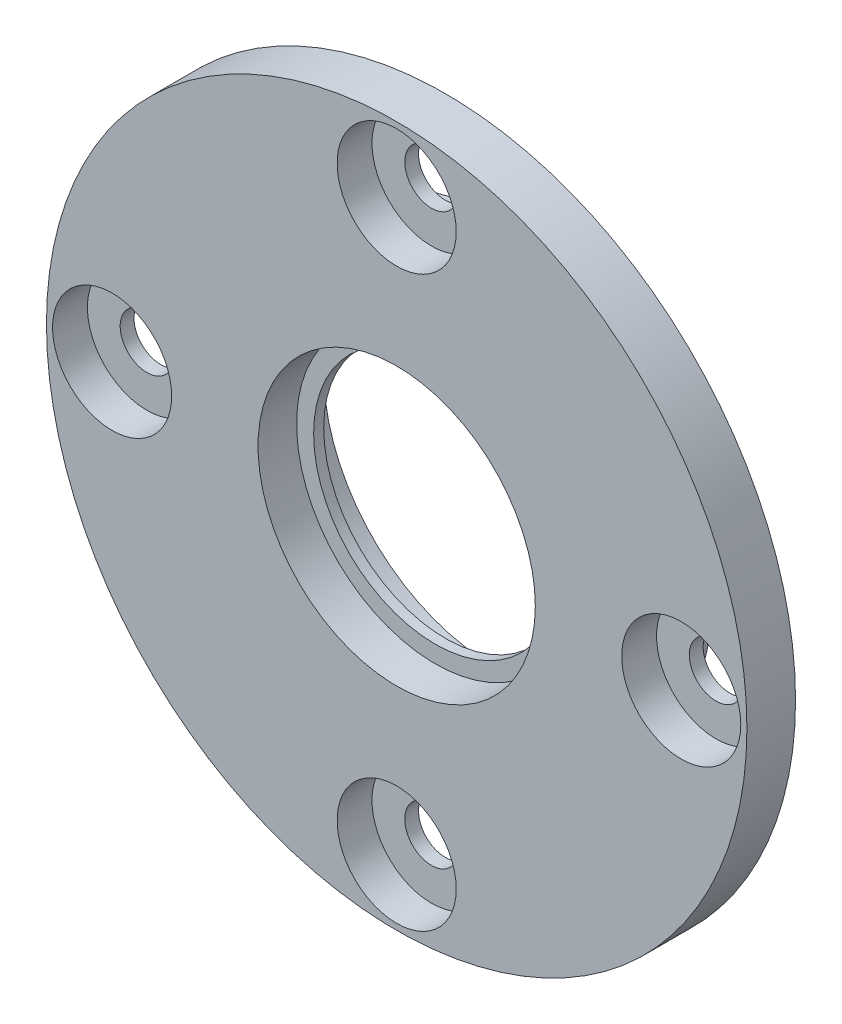
SolidWorks part; units mm, degrees
ref_plane "Front Plane" through (0, 0, 0) normal (0, 0, 1) x (1, 0, 0)
ref_plane "Top Plane" through (0, 0, 0) normal (0, 1, 0) x (1, 0, 0)
ref_plane "Right Plane" through (0, 0, 0) normal (1, 0, 0) x (0, 0, -1)
sketch "Sketch1" plane through (0, 0, 0) normal (1, 0, 0) x (0, 0, -1)
  line L0 (-109.9, -9.5) -> (-139, -9.5)
  line L5 (-1000, 0) -> (49000, 0)
  line L6 (0, -9.5) -> (0, 9.5)
  line L13 (0, 9.5) -> (-48.3, 9.5)
  line L26 (-48.3, 9.5) -> (-48.3, 14)
  line L27 (-48.3, 14) -> (-109.9, 14)
  line L32 (-109.9, 14) -> (-109.9, 9.5)
  line L34 (-155, 7) -> (-155, -7)
  line L36 (-109.9, -9.5) -> (-109.9, -14)
  line L37 (-109.9, -14) -> (-48.3, -14)
  line L38 (-48.3, -14) -> (-48.3, -9.5)
  line L39 (0, -9.5) -> (-48.3, -9.5)
  line L40 (-20.2, 36) -> (-15.2, 36)
  line L41 (-126.5, 22.5) -> (-109.9, 22.5)
  line L42 (-126.5, 22.5) -> (-126.5, -22.5)
  line L43 (-126.5, -22.5) -> (-109.9, -22.5)
  line L44 (-109.9, 22.5) -> (-109.9, -22.5)
  line L45 (-126.5, 22.5) -> (-109.9, -22.5) construction
  line L46 (-126.5, -22.5) -> (-109.9, 22.5) construction
  line L47 (-31.7, 22.5) -> (-48.3, 22.5)
  line L48 (-31.7, 22.5) -> (-31.7, -22.5)
  line L49 (-31.7, -22.5) -> (-48.3, -22.5)
  line L50 (-48.3, 22.5) -> (-48.3, -22.5)
  line L51 (-31.7, 22.5) -> (-48.3, -22.5) construction
  line L52 (-31.7, -22.5) -> (-48.3, 22.5) construction
  line L59 (-15.2, 36) -> (-15.2, -36)
  line L60 (-15.2, -36) -> (-20.2, -36)
  line L61 (-20.2, -22.5) -> (-25.2, -22.5)
  line L62 (-25.2, -22.5) -> (-25.2, -17.5)
  line L63 (-25.2, -17.5) -> (-20.2, -17.5)
  line L64 (-20.2, -17.5) -> (-20.2, 17.5)
  line L65 (-20.2, 17.5) -> (-25.2, 17.5)
  line L66 (-25.2, 17.5) -> (-25.2, 22.5)
  line L67 (-25.2, 22.5) -> (-20.2, 22.5)
  line L68 (-20.2, 22.5) -> (-20.2, 36)
  line L69 (-20.2, -22.5) -> (-20.2, -36)
  line L71 (-131.5, 36) -> (-21.2, 36)
  line L72 (-131.5, 36) -> (-131.5, -36)
  line L73 (-131.5, -36) -> (-21.2, -36)
  line L74 (-21.2, 36) -> (-21.2, -36)
  line L75 (-131.5, 36) -> (-21.2, -36) construction
  line L76 (-131.5, -36) -> (-21.2, 36) construction
  line L77 (-139, -9.5) -> (-139, -7)
  line L78 (-139, -7) -> (-155, -7)
  line L79 (-109.9, 9.5) -> (-139, 9.5)
  line L80 (-139, 7) -> (-155, 7)
  line L81 (-139, 9.5) -> (-139, 7)
  line L82 (-124.45, 9.5) -> (-124.45, -9.5) construction
  line L83 (-24.15, 9.5) -> (-24.15, -9.5) construction
  line L96 (-131.5, 36) -> (-136.5, 36)
  line L97 (-131.5, 36) -> (-131.5, 22.5)
  line L98 (-131.5, -36) -> (-136.5, -36)
  line L99 (-136.5, 36) -> (-136.5, -36)
  line L100 (-131.5, 17.5) -> (-126.5, 17.5)
  line L102 (-131.5, 22.5) -> (-126.5, 22.5)
  line L103 (-126.5, 17.5) -> (-126.5, 22.5)
  line L104 (-131.5, -22.5) -> (-126.5, -22.5)
  line L106 (-131.5, -17.5) -> (-126.5, -17.5)
  line L107 (-126.5, -22.5) -> (-126.5, -17.5)
  line L108 (-131.5, -22.5) -> (-131.5, -36)
  line L109 (-131.5, 17.5) -> (-131.5, -17.5)
  point P3 (0, 0)
  point P18 (-118.2, 0)
  point P24 (-40, 0)
  point P29 (-76.35, 0)
  point P48 (-15.2, 29.25)
  point P70 (-136.5, 29.25)
revolve "Main_body" add sketch "Sketch1" angle 360 about L5 region at (0, 22.75, 134) region at (0, 20, 129)
sketch "Sketch2" plane through (0, 0, 131.5) normal (0, 0, -1) x (-1, 0, 0)
  circle A0 centre (0, 0) radius 12.5
  dimension "D1" = 25
extrude "Shaft_thru" cut sketch "Sketch2" against normal through all
hole_wizard "CBORE for M5 Hex Head Bolt1" positions "Sketch3" profile "Sketch4" counterbore size "M5" standard "ANSI Metric" end condition through all
sketch "Sketch3" plane through (0, 0, 136.5) normal (0, 0, 1) x (1, 0, 0)
  point P0 (0, 29.25)
sketch "Sketch4" plane through (0, 29.25, 136.5) normal (1, 0, 0) x (0, -1, 0)
  line L0 (0, 0) -> (0, 10)
  line L1 (0, 10) -> (2.75, 10)
  line L3 (2.75, 10) -> (2.75, 3.58)
  line L4 (2.75, 3.58) -> (6.12, 3.58)
  line L5 (6.12, 3.58) -> (6.12, 0)
  line L7 (6.12, 0) -> (0, 0)
  line L11 (0, -6.35) -> (0, 107.95) construction
  dimension "Thru Hole Dia." = 5.5
  dimension "Thru Hole Depth" = 10
  dimension "C'Bore Dia." = 12.24
  dimension "C'Bore Depth" = 3.58
pattern_circular "CirPattern1" count 4 over 360 about axis through (0, 0, 1000) along (0, 0, -1) of "CBORE for M5 Hex Head Bolt1"
sketch "Sketch5" plane through (0, 0, 136.5) normal (0, 0, 1) x (1, 0, 0)
  circle A0 centre (0, 0) radius 14.25
  dimension "D1" = 28.5
extrude "seal_seat" cut sketch "Sketch5" against normal blind 3.9624
